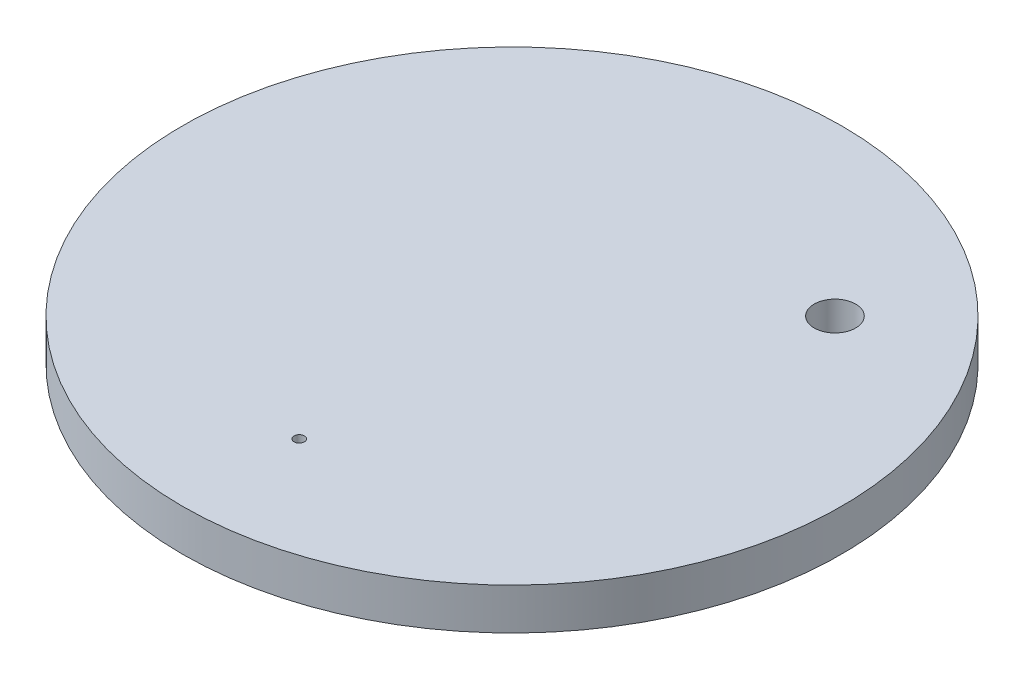
SolidWorks part; units mm, degrees
material "1060 Alloy"
ref_plane "Front Plane" through (0, 0, 0) normal (0, 0, 1) x (1, 0, 0)
ref_plane "Top Plane" through (0, 0, 0) normal (0, 1, 0) x (1, 0, 0)
ref_plane "Right Plane" through (0, 0, 0) normal (1, 0, 0) x (0, 0, -1)
sketch "Sketch1" plane through (0, 0, 0) normal (0, 1, 0) x (1, 0, 0)
  circle A0 centre (0, 0) radius 15.875
  dimension "D1" = 31.75
extrude "Boss-Extrude1" add sketch "Sketch1" along normal blind 1
sketch "Sketch6" plane through (0, 0, 0) normal (0, -1, 0) x (1, 0, 0)
  circle A0 centre (0, 0) radius 15.875
  circle A1 centre (0, 0) radius 9.525
  circle A2 centre (0, 0) radius 15.875 construction
  dimension "D1" = 0
  dimension "D2" = 19.05
extrude "Boss-Extrude3" add sketch "Sketch6" along normal blind 1
thread "Thread1" pitch 0.25 method cut profile "Thread Profile1" start angle 0, offset 0, length 1, pitch 0.25, diameter 19.05
ref_plane "Plane1" through (9.525, -1, 0) normal (0, 0, 1) x (1, 0, 0)
sketch "Thread Profile1" plane through (9.525, -1, 0) normal (0, 0, 1) x (1, 0, 0)
  line L0 (0, 0) -> (0, 0.25) construction
  line L1 (0, 0) -> (0.1353, 0.0781)
  line L2 (0.1353, 0.0781) -> (0.1353, 0.1094)
  line L3 (0.1353, 0.1094) -> (0, 0.1875)
  line L4 (0.1353, 0.0937) -> (0, 0.0937) construction
  line L11 (0, 0) -> (0, 0.1875)
  point P2 (0, 0)
  dimension "Pitch" = 0.25
  dimension "Profile_Angle" = 60
  dimension "Profile_Land" = 0.0312
  dimension "Profile_Height" = 0.1353
sketch "Sketch7" plane through (0, 1, 0) normal (0, 1, 0) x (1, 0, 0)
  circle A0 centre (0, -10.25) radius 0.25
  circle A1 centre (0, 0) radius 9.8
  dimension "D1" = 0.5
  dimension "D2" = 10.25
  dimension "D3" = 19.6
extrude "Cut-Extrude1" cut sketch "Sketch7" against normal through all both and the other way through all contours A1 A0 region at (0, 1, 10.25)
sketch "Sketch8" plane through (0, 1, 0) normal (0, 1, 0) x (1, 0, 0)
  line L0 (0, 0) -> (13.2071, 13.2071) construction
  circle A0 centre (7.7782, 7.7782) radius 1
  dimension "D1" = 2
  dimension "D2" = 11
extrude "Cut-Extrude2" cut sketch "Sketch8" against normal through all both and the other way through all
